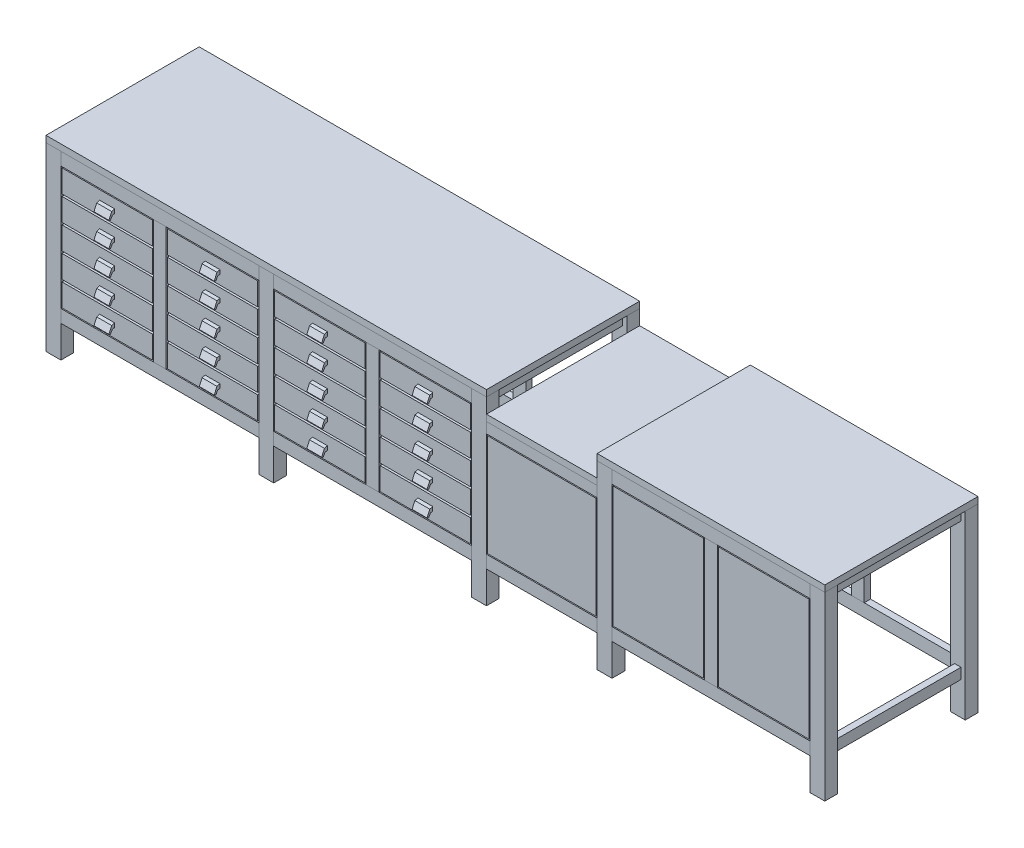
SolidWorks part; units mm, degrees
ref_plane "Front" through (0, 0, 0) normal (0, 0, 1) x (1, 0, 0)
ref_plane "Top" through (0, 0, 0) normal (0, 1, 0) x (1, 0, 0)
ref_plane "Right" through (0, 0, 0) normal (1, 0, 0) x (0, 0, -1)
sketch "Esquisse1" plane through (0, 0, 0) normal (0, 0, 1) x (1, 0, 0)
  line L0 (0, 0) -> (0, 850)
  line L1 (0, 850) -> (70, 850)
  line L2 (70, 850) -> (70, 0)
  line L3 (70, 0) -> (0, 0)
  line L4 (1000, 0) -> (70, 0) construction
  line L5 (1000, 0) -> (1070, 0)
  line L6 (1000, 0) -> (1000, 850)
  line L7 (1000, 850) -> (1070, 850)
  line L8 (1070, 0) -> (1070, 850)
  line L9 (1070, 0) -> (1535, 0) construction
  line L10 (1535, 0) -> (1535, 900) construction
  line L11 (2000, 0) -> (2000, 850)
  line L12 (2070, 850) -> (2000, 850)
  line L13 (2070, 0) -> (2070, 850)
  line L14 (2070, 0) -> (2000, 0)
  line L15 (2070, 0) -> (2330, 0) construction
  line L16 (2330, 0) -> (2330, 550.785) construction
  line L17 (2590, 0) -> (2660, 0)
  line L18 (2590, 0) -> (2590, 850)
  line L19 (2590, 850) -> (2660, 850)
  line L20 (2660, 0) -> (2660, 850)
  line L21 (3590, 0) -> (3590, 850)
  line L22 (3660, 850) -> (3590, 850)
  line L23 (3660, 0) -> (3660, 850)
  line L24 (3660, 0) -> (3590, 0)
  dimension "D1" = 850
  dimension "D2" = 70
  dimension "D3" = 1000
  dimension "D4" = 1000
  dimension "D5" = 520
extrude "Boss.-Extru.1" add sketch "Esquisse1" along normal blind 60
sketch "Esquisse2" plane through (0, 0, 60) normal (0, 0, 1) x (1, 0, 0)
  line L0 (1000, 850) -> (1000, 0) construction
  line L1 (70, 850) -> (1000, 850)
  line L2 (70, 850) -> (70, 790)
  line L3 (70, 790) -> (1000, 790)
  line L4 (1000, 850) -> (1000, 790)
  line L5 (2000, 850) -> (2000, 0) construction
  line L6 (1070, 850) -> (2000, 850)
  line L7 (1070, 850) -> (1070, 790)
  line L8 (1070, 790) -> (2000, 790)
  line L9 (2000, 850) -> (2000, 790)
  line L10 (3590, 850) -> (3590, 0) construction
  line L11 (2660, 850) -> (3590, 850)
  line L12 (2660, 850) -> (2660, 790)
  line L13 (2660, 790) -> (3590, 790)
  line L14 (3590, 850) -> (3590, 790)
  line L15 (70, 500) -> (911.6674, 500) construction
  line L16 (70, 0) -> (70, 850) construction
  line L17 (3590, 150) -> (3590, 210)
  line L18 (2660, 210) -> (3590, 210)
  line L19 (2660, 150) -> (2660, 210)
  line L20 (2660, 150) -> (3590, 150)
  line L21 (2000, 150) -> (2000, 210)
  line L22 (1070, 210) -> (2000, 210)
  line L23 (1070, 150) -> (1070, 210)
  line L24 (1070, 150) -> (2000, 150)
  line L25 (1000, 150) -> (1000, 210)
  line L26 (70, 210) -> (1000, 210)
  line L27 (70, 150) -> (70, 210)
  line L28 (70, 150) -> (1000, 150)
  line L29 (2070, 0) -> (2070, 850) construction
  line L30 (2070, 750) -> (2590, 750)
  line L31 (2070, 750) -> (2070, 700)
  line L32 (2070, 700) -> (2590, 700)
  line L33 (2590, 750) -> (2590, 700)
  line L34 (2590, 850) -> (2590, 0) construction
  line L35 (2070, 850) -> (2000, 850) construction
  line L36 (2070, 210) -> (2590, 210)
  line L37 (2070, 210) -> (2070, 150)
  line L38 (2070, 150) -> (2590, 150)
  line L39 (2590, 210) -> (2590, 150)
  dimension "D1" = 700
  dimension "D2" = 60
  dimension "D3" = 100
  dimension "D4" = 50
extrude "Boss.-Extru.2" add sketch "Esquisse2" against normal blind 35 separate body
sketch "Esquisse3" plane through (0, 0, 0) normal (0, 0, -1) x (-1, 0, 0)
  line L0 (-3660, 850) -> (-3590, 850) construction
  line L1 (-3640, 850) -> (-3610, 850)
  line L2 (-3640, 850) -> (-3640, 800)
  line L3 (-3640, 800) -> (-3610, 800)
  line L4 (-3610, 850) -> (-3610, 800)
  line L5 (-3625, 800) -> (-3625, 0) construction
  line L6 (-3590, 0) -> (-3660, 0) construction
  line L7 (-3125, 0) -> (-3125, 850) construction
  line L8 (-3590, 850) -> (-2660, 850) construction
  line L9 (-3625, 502.5) -> (-3943.0825, 502.5) construction
  line L10 (-3610, 155) -> (-3610, 205)
  line L11 (-3640, 205) -> (-3610, 205)
  line L12 (-3640, 155) -> (-3640, 205)
  line L13 (-3640, 155) -> (-3610, 155)
  line L14 (-3590, 180) -> (-3610, 180) construction
  line L15 (-3590, 150) -> (-3590, 210) construction
  line L16 (-2660, 180) -> (-2640, 180) construction
  line L17 (-2610, 155) -> (-2640, 155)
  line L18 (-2610, 155) -> (-2610, 205)
  line L19 (-2610, 205) -> (-2640, 205)
  line L20 (-2640, 155) -> (-2640, 205)
  line L21 (-2640, 850) -> (-2640, 800)
  line L22 (-2610, 800) -> (-2640, 800)
  line L23 (-2610, 850) -> (-2610, 800)
  line L24 (-2610, 850) -> (-2640, 850)
  line L25 (-2330, 700) -> (-2330, 210) construction
  line L26 (-2070, 700) -> (-2590, 700) construction
  line L27 (-2590, 210) -> (-2070, 210) construction
  line L28 (-2000, 180) -> (-2020, 180) construction
  line L29 (-2050, 850) -> (-2020, 850)
  line L30 (-2050, 850) -> (-2050, 800)
  line L31 (-2050, 800) -> (-2020, 800)
  line L32 (-2020, 850) -> (-2020, 800)
  line L33 (-2020, 155) -> (-2020, 205)
  line L34 (-2050, 205) -> (-2020, 205)
  line L35 (-2050, 155) -> (-2050, 205)
  line L36 (-2050, 155) -> (-2020, 155)
  line L37 (-1535, 210) -> (-1535, 790) construction
  line L38 (-2000, 210) -> (-1070, 210) construction
  line L39 (-1070, 790) -> (-2000, 790) construction
  line L40 (-1070, 180) -> (-1050, 180) construction
  line L41 (-1020, 155) -> (-1050, 155)
  line L42 (-1020, 155) -> (-1020, 205)
  line L43 (-1020, 205) -> (-1050, 205)
  line L44 (-1050, 155) -> (-1050, 205)
  line L45 (-1050, 850) -> (-1050, 800)
  line L46 (-1020, 800) -> (-1050, 800)
  line L47 (-1020, 850) -> (-1020, 800)
  line L48 (-1020, 850) -> (-1050, 850)
  line L49 (-535, 210) -> (-535, 790) construction
  line L50 (-1000, 210) -> (-70, 210) construction
  line L51 (-70, 790) -> (-1000, 790) construction
  line L52 (0, 180) -> (-20, 180) construction
  line L53 (-50, 850) -> (-20, 850)
  line L54 (-50, 850) -> (-50, 800)
  line L55 (-50, 800) -> (-20, 800)
  line L56 (-20, 850) -> (-20, 800)
  line L57 (-20, 155) -> (-20, 205)
  line L58 (-50, 205) -> (-20, 205)
  line L59 (-50, 155) -> (-50, 205)
  line L60 (-50, 155) -> (-20, 155)
  dimension "D1" = 50
  dimension "D2" = 30
extrude "Boss.-Extru.3" add sketch "Esquisse3" along normal blind 600 separate body
extrude "Boss.-Extru.4" add sketch "Esquisse1<2>" against normal blind 60 from vertex separate body starting at point (3640, 850, -600)
sketch "Esquisse1<2>" plane through (0, 0, 0) normal (0, 0, 1) x (1, 0, 0) same geometry as "Esquisse1"
extrude "Boss.-Extru.5" add sketch "Esquisse2<2>" along normal blind 30 from vertex separate body starting at point (2000, 850, -660)
sketch "Esquisse2<2>" plane through (0, 0, 60) normal (0, 0, 1) x (1, 0, 0) same geometry as "Esquisse2"
sketch "Esquisse4" plane through (0, 850, 0) normal (0, 1, 0) x (1, 0, 0)
  line L1 (0, 660) -> (2070, 660)
  line L2 (0, 660) -> (0, -60)
  line L3 (0, -60) -> (2070, -60)
  line L4 (2070, 660) -> (2070, -60)
  line L5 (2590, 660) -> (3660, 660)
  line L6 (2590, 660) -> (2590, -60)
  line L7 (2590, -60) -> (3660, -60)
  line L8 (3660, 660) -> (3660, -60)
extrude "Boss.-Extru.6" add sketch "Esquisse4" along normal blind 30 separate body
sketch "Esquisse5" plane through (0, 750, 0) normal (0, 1, 0) x (1, 0, 0)
  line L1 (2070, 660) -> (2590, 660)
  line L2 (2070, 660) -> (2070, -60)
  line L3 (2070, -60) -> (2590, -60)
  line L4 (2590, 660) -> (2590, -60)
extrude "Boss.-Extru.7" add sketch "Esquisse5" along normal blind 30 separate body
sketch "Esquisse6" plane through (0, 0, 60) normal (0, 0, 1) x (1, 0, 0)
  line L0 (1000, 210) -> (70, 210) construction
  line L1 (505, 210) -> (565, 210)
  line L2 (505, 210) -> (505, 790)
  line L3 (505, 790) -> (565, 790)
  line L4 (565, 210) -> (565, 790)
  line L5 (70, 790) -> (1000, 790) construction
  line L6 (535, 790) -> (535, 210) construction
  line L7 (1035, 210) -> (1035, 790) construction
  line L8 (2000, 210) -> (1070, 210) construction
  line L9 (1070, 790) -> (2000, 790) construction
  line L10 (1535, 790) -> (1535, 210) construction
  line L11 (1505, 210) -> (1505, 790)
  line L12 (1565, 790) -> (1505, 790)
  line L13 (1565, 210) -> (1565, 790)
  line L14 (1565, 210) -> (1505, 210)
  line L15 (2330, 210) -> (2330, 790) construction
  line L16 (3125, 790) -> (3125, 210) construction
  line L17 (3095, 210) -> (3155, 210)
  line L18 (3095, 210) -> (3095, 790)
  line L19 (3095, 790) -> (3155, 790)
  line L20 (3155, 210) -> (3155, 790)
  line L21 (2660, 790) -> (3590, 790) construction
  point P30 (3043.2881, 790)
  point P31 (3244.3933, 790)
  point P34 (3125, 790)
  dimension "D1" = 60
extrude "Boss.-Extru.8" add sketch "Esquisse6" against normal up to vertex (35 mm away) separate body up to point (3590, 210, 25)
extrude "Boss.-Extru.10" add sketch "Esquisse6<2>" along normal up to vertex (-690 mm away) from vertex separate body up to point (2000, 210, -630) starting at point (2000, 210, -660)
sketch "Esquisse6<2>" plane through (0, 0, 60) normal (0, 0, 1) x (1, 0, 0) same geometry as "Esquisse6"
sketch "Esquisse7" plane through (0, 0, 60) normal (0, 0, 1) x (1, 0, 0)
  line L0 (505, 790) -> (505, 210) construction
  line L1 (75, 215) -> (500, 215)
  line L2 (75, 215) -> (75, 321)
  line L3 (75, 321) -> (500, 321)
  line L4 (500, 215) -> (500, 321)
  line L5 (70, 0) -> (70, 850) construction
  line L6 (1000, 210) -> (70, 210) construction
  line L7 (287.5, 321) -> (287.5, 326) construction
  line L8 (287.5, 326) -> (85.6417, 326) construction
  line L9 (500, 437) -> (500, 331)
  line L10 (75, 331) -> (500, 331)
  line L11 (75, 437) -> (75, 331)
  line L12 (75, 437) -> (500, 437)
  line L13 (70, 442) -> (505, 442) construction
  line L14 (287.5, 558) -> (85.6417, 558) construction
  line L15 (287.5, 563) -> (287.5, 558) construction
  line L16 (75, 447) -> (500, 447)
  line L17 (75, 447) -> (75, 553)
  line L18 (75, 553) -> (500, 553)
  line L19 (500, 447) -> (500, 553)
  line L20 (500, 669) -> (500, 563)
  line L21 (75, 563) -> (500, 563)
  line L22 (75, 669) -> (75, 563)
  line L23 (75, 669) -> (500, 669)
  line L24 (70, 674) -> (505, 674) construction
  line L25 (287.5, 785) -> (287.5, 790) construction
  line L26 (287.5, 790) -> (85.6417, 790) construction
  line L27 (75, 679) -> (500, 679)
  line L28 (75, 679) -> (75, 785)
  line L29 (75, 785) -> (500, 785)
  line L30 (500, 679) -> (500, 785)
  line L31 (535, 150) -> (535, 880) construction
  line L32 (70, 150) -> (1000, 150) construction
  line L33 (0, 880) -> (2070, 880) construction
  line L34 (782.5, 790) -> (984.3583, 790) construction
  line L35 (782.5, 785) -> (782.5, 790) construction
  line L36 (1000, 674) -> (565, 674) construction
  line L37 (782.5, 563) -> (782.5, 558) construction
  line L38 (782.5, 558) -> (984.3583, 558) construction
  line L39 (1000, 442) -> (565, 442) construction
  line L40 (782.5, 326) -> (984.3583, 326) construction
  line L41 (782.5, 321) -> (782.5, 326) construction
  line L42 (570, 679) -> (570, 785)
  line L43 (995, 785) -> (570, 785)
  line L44 (995, 679) -> (995, 785)
  line L45 (995, 679) -> (570, 679)
  line L46 (995, 669) -> (570, 669)
  line L47 (995, 669) -> (995, 563)
  line L48 (995, 563) -> (570, 563)
  line L49 (570, 669) -> (570, 563)
  line L50 (570, 447) -> (570, 553)
  line L51 (995, 553) -> (570, 553)
  line L52 (995, 447) -> (995, 553)
  line L53 (995, 447) -> (570, 447)
  line L54 (995, 437) -> (570, 437)
  line L55 (995, 437) -> (995, 331)
  line L56 (995, 331) -> (570, 331)
  line L57 (570, 437) -> (570, 331)
  line L58 (570, 215) -> (570, 321)
  line L59 (995, 321) -> (570, 321)
  line L60 (995, 215) -> (995, 321)
  line L61 (995, 215) -> (570, 215)
  line L62 (1035, 0) -> (1035, 880) construction
  line L63 (1000, 0) -> (1070, 0) construction
  line L64 (1287.5, 321) -> (1287.5, 326) construction
  line L65 (1287.5, 326) -> (1085.6417, 326) construction
  line L66 (1070, 442) -> (1505, 442) construction
  line L67 (1287.5, 558) -> (1085.6417, 558) construction
  line L68 (1287.5, 563) -> (1287.5, 558) construction
  line L69 (1070, 674) -> (1505, 674) construction
  line L70 (1287.5, 785) -> (1287.5, 790) construction
  line L71 (1287.5, 790) -> (1085.6417, 790) construction
  line L72 (1535, 150) -> (1535, 880) construction
  line L73 (1782.5, 790) -> (1984.3583, 790) construction
  line L74 (1782.5, 785) -> (1782.5, 790) construction
  line L75 (2000, 674) -> (1565, 674) construction
  line L76 (1782.5, 563) -> (1782.5, 558) construction
  line L77 (1782.5, 558) -> (1984.3583, 558) construction
  line L78 (2000, 442) -> (1565, 442) construction
  line L79 (1782.5, 326) -> (1984.3583, 326) construction
  line L80 (1782.5, 321) -> (1782.5, 326) construction
  line L81 (1075, 215) -> (1500, 215)
  line L82 (1075, 215) -> (1075, 321)
  line L83 (1075, 321) -> (1500, 321)
  line L84 (1500, 215) -> (1500, 321)
  line L85 (1500, 437) -> (1500, 331)
  line L86 (1075, 331) -> (1500, 331)
  line L87 (1075, 437) -> (1075, 331)
  line L88 (1075, 437) -> (1500, 437)
  line L89 (1075, 447) -> (1500, 447)
  line L90 (1075, 447) -> (1075, 553)
  line L91 (1075, 553) -> (1500, 553)
  line L92 (1500, 447) -> (1500, 553)
  line L93 (1500, 669) -> (1500, 563)
  line L94 (1075, 563) -> (1500, 563)
  line L95 (1075, 669) -> (1075, 563)
  line L96 (1075, 669) -> (1500, 669)
  line L97 (1075, 679) -> (1500, 679)
  line L98 (1075, 679) -> (1075, 785)
  line L99 (1075, 785) -> (1500, 785)
  line L100 (1500, 679) -> (1500, 785)
  line L101 (1570, 679) -> (1570, 785)
  line L102 (1995, 785) -> (1570, 785)
  line L103 (1995, 679) -> (1995, 785)
  line L104 (1995, 679) -> (1570, 679)
  line L105 (1995, 669) -> (1570, 669)
  line L106 (1995, 669) -> (1995, 563)
  line L107 (1995, 563) -> (1570, 563)
  line L108 (1570, 669) -> (1570, 563)
  line L109 (1570, 447) -> (1570, 553)
  line L110 (1995, 553) -> (1570, 553)
  line L111 (1995, 447) -> (1995, 553)
  line L112 (1995, 447) -> (1570, 447)
  line L113 (1995, 437) -> (1570, 437)
  line L114 (1995, 437) -> (1995, 331)
  line L115 (1995, 331) -> (1570, 331)
  line L116 (1570, 437) -> (1570, 331)
  line L117 (1570, 215) -> (1570, 321)
  line L118 (1995, 321) -> (1570, 321)
  line L119 (1995, 215) -> (1995, 321)
  line L120 (1995, 215) -> (1570, 215)
  line L121 (2070, 700) -> (2590, 700) construction
  line L122 (2075, 215) -> (2585, 215)
  line L123 (2075, 215) -> (2075, 695)
  line L124 (2075, 695) -> (2585, 695)
  line L125 (2585, 215) -> (2585, 695)
  line L126 (2590, 850) -> (2590, 0) construction
  line L127 (2070, 0) -> (2070, 850) construction
  line L128 (2590, 210) -> (2070, 210) construction
  line L129 (2660, 790) -> (3590, 790) construction
  line L130 (2665, 215) -> (3090, 215)
  line L131 (2665, 215) -> (2665, 785)
  line L132 (2665, 785) -> (3090, 785)
  line L133 (3090, 215) -> (3090, 785)
  line L134 (2660, 0) -> (2660, 850) construction
  line L135 (3590, 210) -> (2660, 210) construction
  line L136 (3095, 790) -> (3095, 210) construction
  line L137 (3125, 210) -> (3125, 790) construction
  line L138 (3160, 215) -> (3160, 785)
  line L139 (3585, 785) -> (3160, 785)
  line L140 (3585, 215) -> (3585, 785)
  line L141 (3585, 215) -> (3160, 215)
  dimension "D1" = 5
  dimension "D2" = 106
  dimension "D3" = 5
  dimension "D4" = 5
  dimension "D5" = 10
  dimension "D6" = 10
  dimension "D7" = 10
  dimension "D8" = 5
  dimension "D9" = 5
  dimension "D10" = 5
  dimension "D11" = 5
  dimension "D12" = 5
  dimension "D13" = 5
  dimension "D14" = 5
  dimension "D15" = 5
extrude "Boss.-Extru.11" add sketch "Esquisse7" against normal blind 18 separate body
sketch "Esquisse8" plane through (0, 0, 0) normal (-1, 0, 0) x (0, 0, 1)
  line L0 (60, 722) -> (60, 742)
  line L1 (60, 850) -> (60, 0) construction
  line L2 (60, 742) -> (73.956, 738.0458)
  line L3 (73.956, 738.0458) -> (87.0637, 708.8535)
  line L4 (87.0637, 708.8535) -> (80.1768, 704.7828)
  line L5 (80.1768, 704.7828) -> (70, 722)
  line L6 (70, 722) -> (60, 722)
  line L7 (42, 732) -> (60, 732) construction
  line L8 (42, 785) -> (42, 679) construction
  line L9 (42, 616) -> (60, 616) construction
  line L10 (42, 669) -> (42, 563) construction
  line L11 (0, 672.9144) -> (127.5941, 672.9144) construction
  line L12 (0, 850) -> (0, 0) construction
  line L13 (60, 606) -> (60, 626)
  line L14 (60, 626) -> (73.956, 622.0458)
  line L15 (73.956, 622.0458) -> (87.0637, 592.8535)
  line L16 (87.0637, 592.8535) -> (80.1768, 588.7828)
  line L17 (80.1768, 588.7828) -> (70, 606)
  line L18 (70, 606) -> (60, 606)
  line L19 (60, 490) -> (60, 510)
  line L20 (60, 510) -> (73.956, 506.0458)
  line L21 (73.956, 506.0458) -> (87.0637, 476.8535)
  line L22 (87.0637, 476.8535) -> (80.1768, 472.7828)
  line L23 (80.1768, 472.7828) -> (70, 490)
  line L24 (70, 490) -> (60, 490)
  line L25 (60, 374) -> (60, 394)
  line L26 (60, 394) -> (73.956, 390.0458)
  line L27 (73.956, 390.0458) -> (87.0637, 360.8535)
  line L28 (87.0637, 360.8535) -> (80.1768, 356.7828)
  line L29 (80.1768, 356.7828) -> (70, 374)
  line L30 (70, 374) -> (60, 374)
  line L31 (60, 258) -> (60, 278)
  line L32 (60, 278) -> (73.956, 274.0458)
  line L33 (73.956, 274.0458) -> (87.0637, 244.8535)
  line L34 (87.0637, 244.8535) -> (80.1768, 240.7828)
  line L35 (80.1768, 240.7828) -> (70, 258)
  line L36 (70, 258) -> (60, 258)
  point P17 (0, 0)
  point P45 (60, 600.1817)
  point P46 (54.6462, 616)
  point P47 (84.7817, 705.222)
  point P48 (87.9109, 708.6135)
  dimension "D1" = 20
  dimension "D2" = 10
  dimension "D3" = 20
  dimension "D4" = 130
  dimension "D6" = 32
  dimension "D7" = 8
  dimension "D9" = 5
extrude "Boss.-Extru.12" add sketch "Esquisse8" against normal up to vertex (1995 mm away) separate body up to point (1995, 785, 60)
sketch "Esquisse9" plane through (0, 0, 60) normal (0, 0, 1) x (1, 0, 0)
  line L0 (0, 850) -> (0, 0) construction
  line L1 (0, 150) -> (252.5, 150)
  line L2 (0, 150) -> (0, 880)
  line L3 (0, 880) -> (252.5, 880)
  line L4 (252.5, 150) -> (252.5, 880)
  line L5 (0, 880) -> (2070, 880) construction
  line L6 (287.5, 215) -> (287.5, 785) construction
  line L7 (75, 215) -> (500, 215) construction
  line L8 (500, 785) -> (75, 785) construction
  line L9 (1035, 0) -> (1035, 880) construction
  line L10 (1000, 0) -> (1070, 0) construction
  line L11 (1817.5, 150) -> (1817.5, 880)
  line L12 (2070, 880) -> (1817.5, 880)
  line L13 (70, 150) -> (1000, 150) construction
  line L14 (2070, 150) -> (2070, 880)
  line L16 (2070, 150) -> (1817.5, 150)
  line L17 (1747.5, 880) -> (1322.5, 880)
  line L18 (322.5, 150) -> (747.5, 150)
  line L19 (322.5, 150) -> (322.5, 880)
  line L20 (322.5, 880) -> (747.5, 880)
  line L21 (747.5, 150) -> (747.5, 880)
  line L22 (1322.5, 150) -> (1322.5, 880)
  line L23 (1747.5, 150) -> (1322.5, 150)
  line L24 (1747.5, 150) -> (1747.5, 880)
  line L25 (1035, 149.7323) -> (817.5, 150)
  line L27 (817.5, 150) -> (817.5, 880)
  line L28 (817.5, 880) -> (1252.5, 880)
  line L29 (1252.5, 150) -> (1252.5, 880)
  line L30 (1035, 149.7323) -> (1252.5, 150)
  line L34 (782.5, 215) -> (782.5, 150) construction
  line L35 (570, 215) -> (995, 215) construction
  point P38 (287.5, 500)
  dimension "D1" = 70
  dimension "D2" = 35
  dimension "D3" = 70
  dimension "D4" = 35
extrude "Enlèv. mat.-Extru.2" cut sketch "Esquisse9" along normal through all
